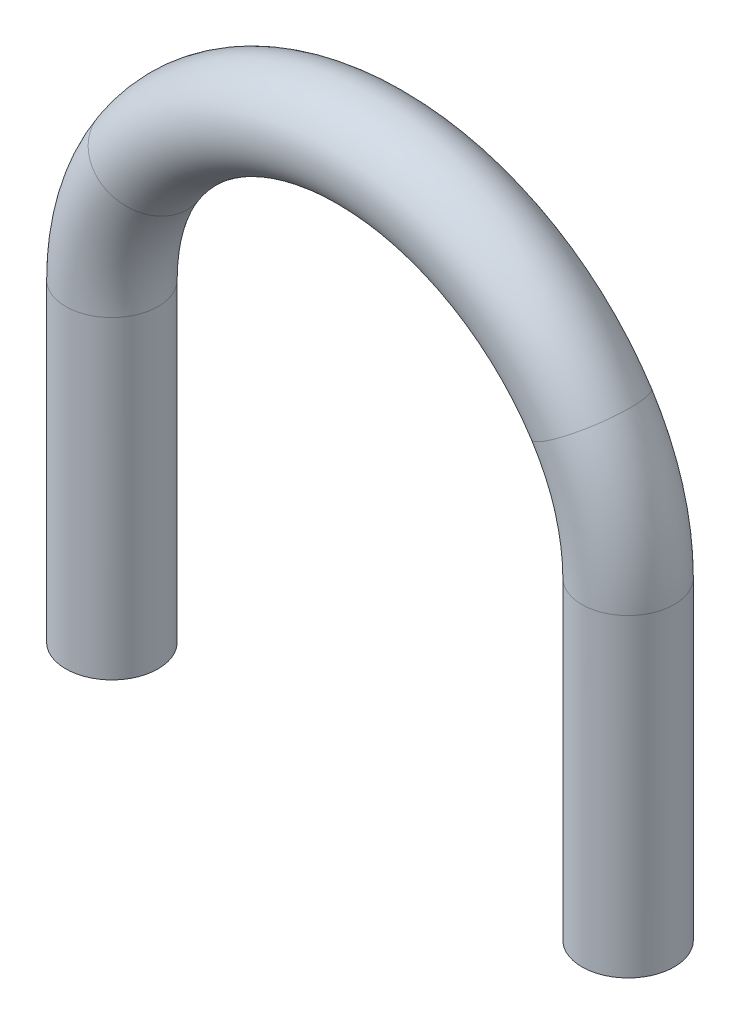
SolidWorks part; units mm, degrees
ref_plane "Front Plane" through (0, 0, 0) normal (0, 0, 1) x (1, 0, 0)
ref_plane "Top Plane" through (0, 0, 0) normal (0, 1, 0) x (1, 0, 0)
ref_plane "Right Plane" through (0, 0, 0) normal (1, 0, 0) x (0, 0, -1)
sketch "Sketch5" plane through (0, 0, 0) normal (0, 0, 1) x (1, 0, 0)
  arc A0 (51.9518, 47.3578) -> (3.9511, 47.3578) centre (27.9514, 31.8146) ccw
  arc A1 (55.9029, 33.9883) -> (51.9518, 47.3578) centre (31.3079, 33.9883) ccw
  arc A2 (0, 33.9883) -> (3.9511, 47.3578) centre (24.595, 33.9883) cw
  spline S0 degree 3 poles (0, 0) (0, 11.3294) (0, 22.6589) (0, 33.9883) knots 0 0 0 0 0.898173 0.898173 0.898173 0.898173
  spline S1 degree 3 poles (55.9029, 0) (55.9029, 11.3294) (55.9029, 22.6589) (55.9029, 33.9883) knots 0 0 0 0 0.898173 0.898173 0.898173 0.898173
  dimension "D1" = 24.595
sweep "Sweep1" add path "Sketch5" circular profile diameter 10 parameters "D3"=10
scale "Scale7" scale about centroid uniform scaling yes scale factor 2.5
